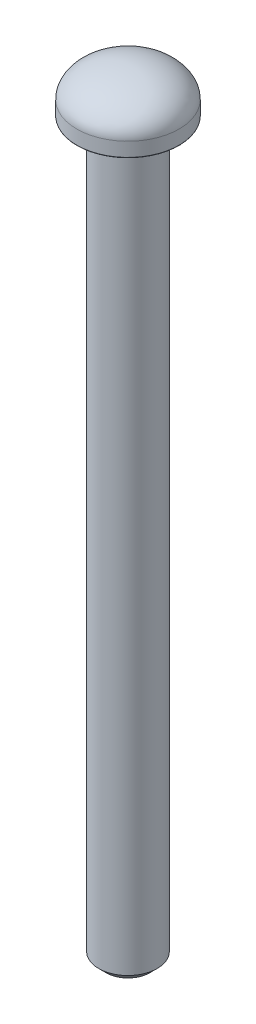
SolidWorks part; units mm, degrees
ref_plane "Front" through (0, 0, 0) normal (0, 0, 1) x (1, 0, 0)
ref_plane "Top" through (0, 0, 0) normal (0, 1, 0) x (1, 0, 0)
ref_plane "Right" through (0, 0, 0) normal (1, 0, 0) x (0, 0, -1)
sketch "Sketch1" plane through (0, 0, 0) normal (0, 1, 0) x (1, 0, 0)
  circle A0 centre (0, 0) radius 4
  dimension "D1" = 8
extrude "Boss-Extrude1" add sketch "Sketch1" along normal blind 100
sketch "Sketch2" plane through (0, 100, 0) normal (0, 1, 0) x (1, 0, 0)
  circle A1 centre (0, 0) radius 7
extrude "Boss-Extrude2" add sketch "Sketch2" along normal blind 2
dome "Dome1" faces to dome 1 distance 4 reverse direction no elliptical dome yes face at (0, 102, 7) parameters "D1"=4
fillet "Fillet1" radius 0.1 2 edges at (0, 100, 7) (0, 100, 4)
chamfer "Chamfer1" distance 1 angle 45 1 edges at (0, 0, 4)
